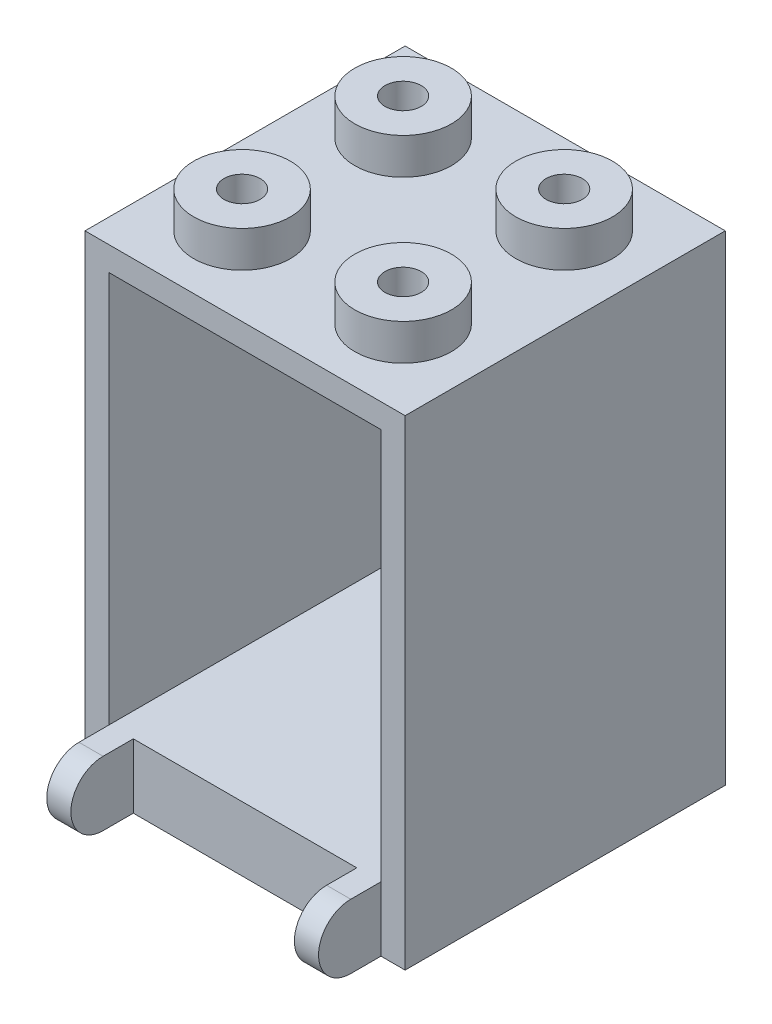
SolidWorks part; units mm, degrees
ref_plane "Front Plane" through (0, 0, 0) normal (0, 0, 1) x (1, 0, 0)
ref_plane "Top Plane" through (0, 0, 0) normal (0, 1, 0) x (1, 0, 0)
ref_plane "Right Plane" through (0, 0, 0) normal (1, 0, 0) x (0, 0, -1)
sketch "Sketch1" plane through (0, 0, 0) normal (0, 0, 1) x (1, 0, 0)
  line L1 (-7.95, -11.925) -> (7.95, -11.925)
  line L2 (-7.95, -11.925) -> (-7.95, 11.925)
  line L3 (-7.95, 11.925) -> (7.95, 11.925)
  line L4 (7.95, -11.925) -> (7.95, 11.925)
  line L5 (-7.95, -11.925) -> (7.95, 11.925) construction
  line L6 (-7.95, 11.925) -> (7.95, -11.925) construction
  point P0 (0, 0)
  dimension "D1" = 23.85
  dimension "D2" = 15.9
extrude "Boss-Extrude1" add sketch "Sketch1" against normal blind 15.9
shell "Shell2" thickness 1.2 removed face at (0, 0, 0)
sketch "Sketch7" plane through (0, -10.725, 0) normal (0, 1, 0) x (1, 0, 0)
  line L4 (-6.75, 0) -> (6.75, 0)
  line L5 (6.75, 0) -> (6.75, 14.7)
  line L6 (6.75, 14.7) -> (-6.75, 14.7)
  line L7 (-6.75, 14.7) -> (-6.75, 0)
  line L8 (-6.75, 0) -> (6.75, 0)
  line L9 (6.75, 0) -> (6.75, 14.7)
  line L10 (6.75, 14.7) -> (-6.75, 14.7)
  line L11 (-6.75, 14.7) -> (-6.75, 0)
  dimension "D1" = 0
extrude "Boss-Extrude4" add sketch "Sketch7" along normal blind 2
ref_plane "Plane1" through (6.75, 0, 0) normal (1, 0, 0) x (0, 0, -1)
shell "Shell3" thickness 1.2 removed face at (0, -11.925, -7.95)
sketch "Sketch5" plane through (6.75, 0, 0) normal (1, 0, 0) x (0, 0, -1)
  line L0 (0, -11.925) -> (-1.5, -11.925)
  line L1 (0, -11.925) -> (0, -8.725)
  line L2 (0, -8.725) -> (-1.5, -8.725)
  line L3 (-1.5, -8.725) -> (-1.5, -11.925) construction
  arc A0 (-1.5, -8.725) -> (-1.5, -11.925) centre (-1.5, -10.325) ccw
  dimension "D1" = 3.2
  dimension "D2" = 1.5
extrude "Boss-Extrude3" add sketch "Sketch5" against normal blind 1.2
mirror "Mirror2" about plane through (0, 0, 0) normal (1, 0, 0) of "Boss-Extrude3"
sketch "Sketch8" plane through (0, 0, -14.7) normal (0, 0, 1) x (1, 0, 0)
  line L0 (-4.25, 10.725) -> (-4.25, 7.925)
  line L1 (6.75, 10.725) -> (-6.75, 10.725) construction
  line L2 (-4.25, 7.925) -> (4.25, 7.925)
  line L3 (4.25, 7.925) -> (4.25, 10.725)
  line L4 (4.25, 10.725) -> (-4.25, 10.725)
  line L5 (0, 0) -> (0, 10.725) construction
  dimension "D1" = 8.5
  dimension "D2" = 2.8
extrude "Cut-Extrude2" cut sketch "Sketch8" against normal through all
sketch "Sketch9" plane through (0, 0, -14.7) normal (0, 0, 1) x (1, 0, 0)
  line L0 (-4.25, 9.325) -> (-4.75, 9.325)
  line L1 (-4.25, 10.725) -> (-4.25, 7.925) construction
  line L2 (-4.75, 9.325) -> (-4.75, 10.725)
  line L3 (-4.25, 10.725) -> (-6.75, 10.725) construction
  line L4 (-4.75, 10.725) -> (-4.25, 10.725)
  line L5 (-4.25, 10.725) -> (-4.25, 9.325)
  dimension "D1" = 0.5
extrude "Boss-Extrude5" add sketch "Sketch9" along normal blind 12.7
mirror "Mirror3" about plane through (0, 0, 0) normal (1, 0, 0) of "Boss-Extrude5"
sketch "Sketch10" plane through (0, -9.925, 0) normal (0, -1, 0) x (1, 0, 0)
  line L0 (0, 0) -> (0, -16.6604) construction
  line L1 (-6.75, -14.7) -> (6.75, -1.2) construction
  line L3 (6.75, -1.2) -> (6.75, -14.7) construction
  line L4 (6.75, -14.7) -> (-6.75, -1.2) construction
  circle A0 centre (0, -7.95) radius 3.25
  circle A1 centre (0, -7.95) radius 2.4
  dimension "D1" = 6.5
  dimension "D2" = 4.8
extrude "Boss-Extrude6" add sketch "Sketch10" along normal up to surface (2 mm away) up to face at (0, -11.925, -2.15)
sketch "Sketch11" plane through (0, 11.925, 0) normal (0, 1, 0) x (1, 0, 0)
  line L0 (7.95, 0) -> (-7.95, 0) construction
  line L2 (-7.95, 15.9) -> (-7.95, 0) construction
  circle A0 centre (-4.05, 3.9) radius 2.4
  circle A1 centre (-4.05, 3.9) radius 0.9
  dimension "D1" = 4.8
  dimension "D4" = 1.5
  dimension "D2" = 3.9
  dimension "D3" = 3.9
extrude "Boss-Extrude7" add sketch "Sketch11" along normal blind 1.8
pattern_linear "LPattern1" count 2 spacing 8 along (1, 0, 0) count 2 spacing 8 along (0, 0, -1) of "Boss-Extrude7"
